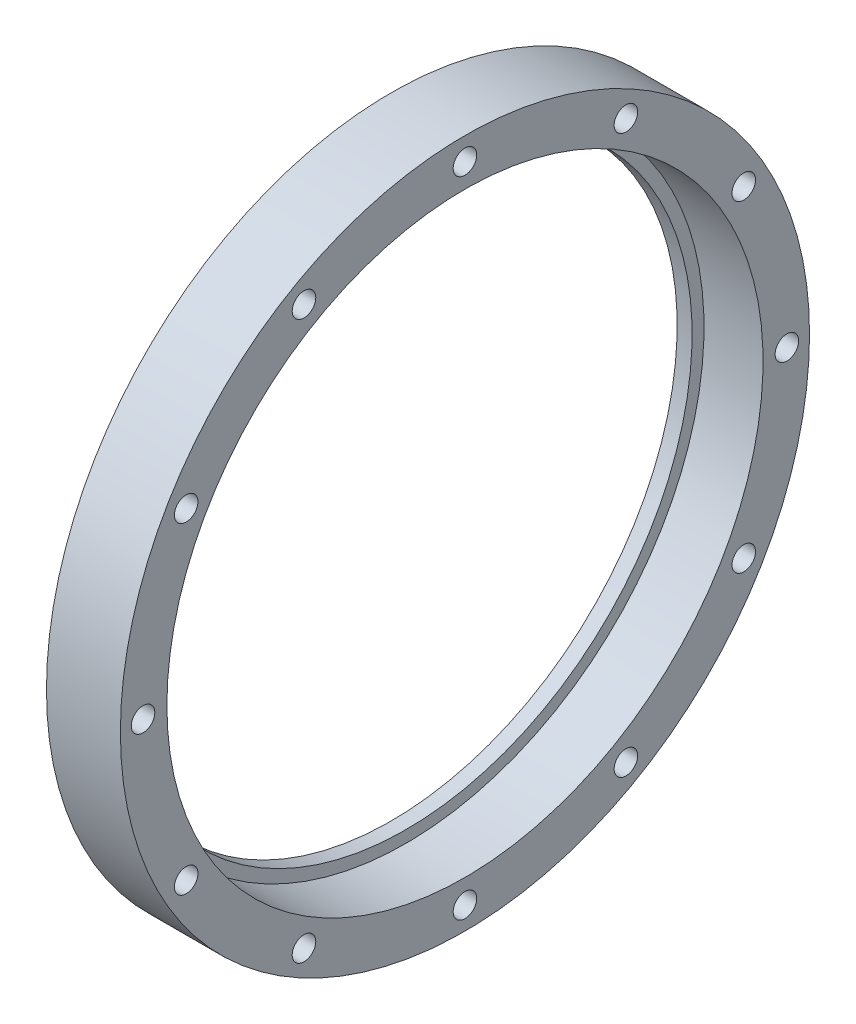
SolidWorks part; units mm, degrees
material "6061 合金"
ref_plane "前视基准面" through (0, 0, 0) normal (0, 0, 1) x (1, 0, 0)
ref_plane "上视基准面" through (0, 0, 0) normal (0, 1, 0) x (1, 0, 0)
ref_plane "右视基准面" through (0, 0, 0) normal (1, 0, 0) x (0, 0, -1)
other "Configuration Table"
sketch "草图1" plane through (0, 0, 0) normal (0, 0, 1) x (1, 0, 0)
  line L0 (0, 0) -> (49657.8442, 0) construction
  line L1 (0, 48) -> (0, 57.8)
  line L2 (0, 48) -> (2.5, 48)
  line L3 (0, 57.8) -> (2.5, 57.8)
  line L4 (2.5, 48) -> (2.5, 57.8)
  line L5 (2.5, 57.8) -> (12.4, 57.8)
  line L6 (2.5, 57.8) -> (2.5, 50)
  line L7 (12.4, 57.8) -> (12.4, 50)
  line L8 (2.5, 50) -> (12.4, 50)
  dimension "D1" = 96
  dimension "D2" = 100
  dimension "D3" = 115.6
  dimension "D4" = 2.5
  dimension "D5" = 9.9
revolve "旋转1" add sketch "草图1" angle 360 about L0 region at (1.25, 52.9, 0) region at (7.45, 53.9, 0)
hole_wizard "M3 螺纹孔1" positions "草图2" profile "草图3" tap size "M3" standard "GB" end condition through all
sketch "草图2" plane through (12.4, 0, 0) normal (1, 0, 0) x (0, 0, -1)
  point P0 (0, 54)
  dimension "D1" = 54
sketch "草图3" plane through (12.4, 54, 0) normal (0, 1, 0) x (0, 0, -1)
  line L0 (0, 0) -> (0, 12.4)
  line L1 (0, 12.4) -> (1.25, 12.4)
  line L2 (1.25, 12.4) -> (1.25, 0)
  line L5 (1.25, 0) -> (0, 0)
  line L11 (0, -6.35) -> (0, 107.95) construction
  dimension "通孔螺纹孔钻头直径" = 2.5
  dimension "通孔螺纹孔钻头深度" = 12.4
cosmetic thread "孔螺蚊线1" parameters "D2"=3
hole_wizard "Ø4.0mm 暗销孔1" positions "草图8" profile "草图9" hole size "Ø4.0" standard "GB"
sketch "草图8" plane through (12.4, 0, 0) normal (1, 0, 0) x (0, 0, -1)
  point P0 (0, 54)
sketch "草图9" plane through (12.4, 54, 0) normal (0, 1, 0) x (0, 0, -1)
  line L0 (0, 0) -> (0, 5.1867)
  line L1 (0, 5.1867) -> (1.975, 4)
  line L2 (1.975, 4) -> (1.975, 0)
  line L5 (1.975, 0) -> (0, 0)
  line L10 (0, 5.1867) -> (-1.975, 4) construction
  line L11 (0, -6.35) -> (0, 107.95) construction
  dimension "孔直径" = 3.95
  dimension "孔深度" = 4
  dimension "导头角度" = 118
pattern_circular "阵列(圆周)1" count 12 over 360 about axis through (0, 0, 0) along (-1, 0, 0) of "M3 螺纹孔1", "Ø4.0mm 暗销孔1" reverse direction yes
shell "抽壳4" [suppressed] thickness 2
fillet "圆角4" [suppressed] type full round
fillet "圆角5" [suppressed] type full round
